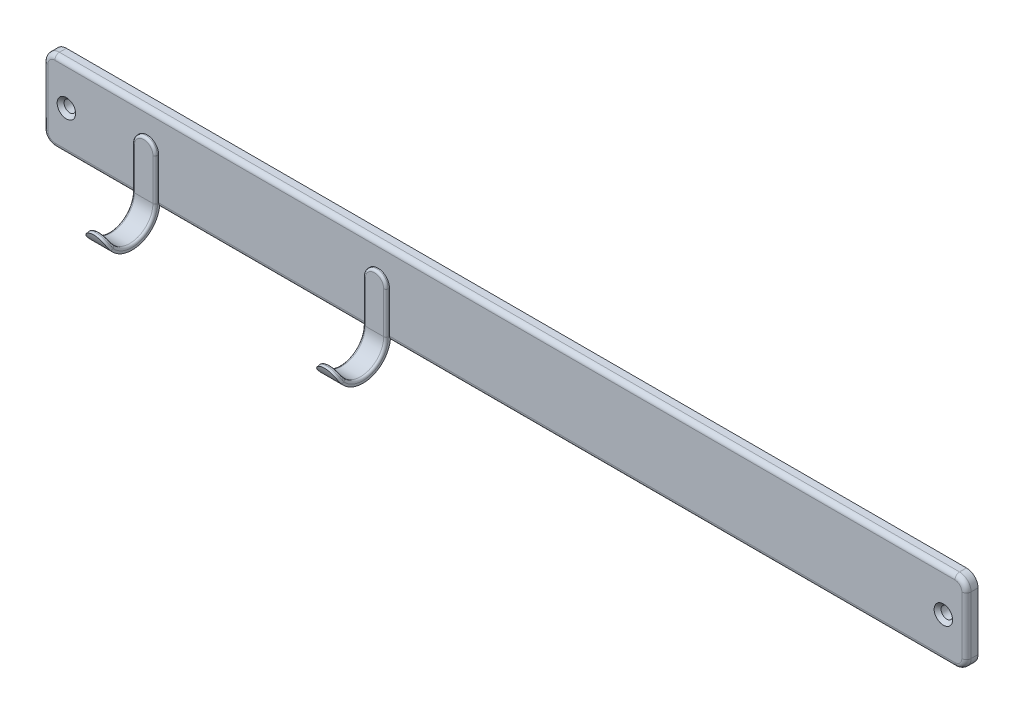
SolidWorks part; units mm, degrees
ref_plane "Front" through (0, 0, 0) normal (0, 0, 1) x (1, 0, 0)
ref_plane "Top" through (0, 0, 0) normal (0, 1, 0) x (1, 0, 0)
ref_plane "Right" through (0, 0, 0) normal (1, 0, 0) x (0, 0, -1)
sketch "Sketch1" plane through (0, 0, 0) normal (0, 0, 1) x (1, 0, 0)
  line L1 (0, 0) -> (400, 0)
  line L2 (0, 0) -> (0, 35)
  line L3 (0, 35) -> (400, 35)
  line L4 (400, 0) -> (400, 35)
  circle A0 centre (10, 17.5) radius 2.5
  circle A1 centre (390, 17.5) radius 2.5
  point P9 (0, 0)
  point P10 (81.7305, 17.5)
  dimension "D3" = 5
  dimension "D4" = 10
  dimension "D5" = 35
  dimension "D1" = 17.5
  dimension "D2" = 10
  dimension "D6" = 400
extrude "Boss-Extrude1" add sketch "Sketch1" along normal blind 5
chamfer "Chamfer1" distance 1.5 angle 45 2 edges at (392.5, 17.5, 5) (12.5, 17.5, 5)
fillet "Fillet1" radius 5 4 edges at (400, 0, 2.5) (400, 35, 2.5) (0, 0, 2.5) (0, 35, 2.5)
fillet "Fillet2" radius 2 8 edges at (398.5355, 33.5355, 5) (400, 17.5, 5) (398.5355, 1.4645, 5) (200, 0, 5) (1.4645, 1.4645, 5) (0, 17.5, 5) (1.4645, 33.5355, 5) (200, 35, 5)
shell "Shell4" thickness 1 removed face at (12.5, 17.5, 0)
sketch "Sketch2" plane through (0, 0, 0) normal (-1, 0, 0) x (0, 0, 1)
  line L0 (4.5, 25) -> (4.5, 2)
  line L1 (0, 35) -> (3, 35) construction
  line L2 (5, 30) -> (5, 5) construction
  arc A0 (4.5, 2) -> (28.119, -1) centre (16.5, 2) ccw
  point P9 (0, 0)
  dimension "D2" = 12
  dimension "D1" = 10
  dimension "D3" = 3
  dimension "D4" = 0.5
extrude "Extrude-Thin1" add sketch "Sketch2" along normal blind 10 from offset 50 thin offset against normal yes thin type one direction reverse wall 2
fillet "Fillet11" 2 edges at (40, 25, 5.75) (50, 25, 5.75) type full round first side face at (40, 4.9576, 11.4482) second side face at (50, 4.9576, 11.4482) middle face at (45, 25, 5.75)
fillet "Fillet12" 2 edges at (40, -0.75, 27.1507) (50, -0.75, 27.1507) type full round first side face at (40, 3.529, 11.4482) second side face at (50, 3.529, 11.4482) middle face at (45, -0.75, 27.1507)
fillet "Fillet13" radius 1 6 edges at (40, 11, 6.5) (45, 25, 6.5) (50, 11, 6.5)
pattern_linear "LPattern3" count 2 spacing 100 along (1, 0, 0) of "Fillet11", "Fillet12", "Fillet13", "Extrude-Thin1"
